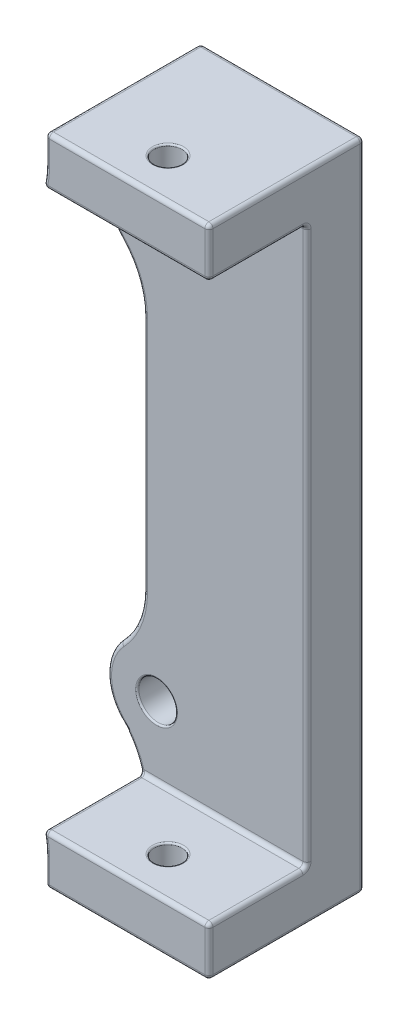
SolidWorks part; units mm, degrees
ref_plane "Front Plane" through (0, 0, 0) normal (0, 0, 1) x (1, 0, 0)
ref_plane "Top Plane" through (0, 0, 0) normal (0, 1, 0) x (1, 0, 0)
ref_plane "Right Plane" through (0, 0, 0) normal (1, 0, 0) x (0, 0, -1)
sketch "Sketch1" plane through (0, 0, 0) normal (0, 0, 1) x (1, 0, 0)
  line L2 (133.4865, -40) -> (139.5, -40) construction
  line L5 (133.4865, 40) -> (139.5, 40) construction
  line L7 (140, -40.5) -> (140, -46.5135) construction
  line L8 (120, 36.5224) -> (120, 40)
  line L9 (140, -40) -> (120, -40)
  line L10 (140, -40) -> (140, 40)
  line L11 (140, 40) -> (120, 40)
  line L12 (120, -40) -> (120, -36.5224)
  line L13 (120, -14.4776) -> (120, 14.4776)
  circle A1 centre (121.5977, 25.5) radius 2.35
  circle A3 centre (121.5977, -25.5) radius 2.35
  arc A4 (117.2486, -21.3666) -> (117.2486, -29.6334) centre (121.5977, -25.5) ccw
  arc A5 (117.2486, 29.6334) -> (117.2486, 21.3666) centre (121.5977, 25.5) ccw
  arc A6 (120, -36.5224) -> (117.2486, -29.6334) centre (110, -36.5224) ccw
  arc A7 (120, -14.4776) -> (117.2486, -21.3666) centre (110, -14.4776) cw
  arc A8 (117.2486, 29.6334) -> (120, 36.5224) centre (110, 36.5224) ccw
  arc A9 (117.2486, 21.3666) -> (120, 14.4776) centre (110, 14.4776) cw
  point P24 (120, 31.2834)
  dimension "D2" = 4.7
  dimension "D3" = 4.7
  dimension "D1" = 10
extrude "Boss-Extrude1" add sketch "Sketch1" along normal blind 7
sketch "Sketch2" plane through (0, 0, 7) normal (0, 0, 1) x (1, 0, 0)
  line L0 (119.6767, 34) -> (140, 34)
  line L1 (140, -34) -> (119.6767, -34)
  line L2 (140, 34) -> (140, 40)
  line L6 (140, -40) -> (140, 40)
  line L7 (140, 40) -> (120, 40)
  line L8 (120, 40) -> (120, 36.5224)
  line L9 (120, 14.4776) -> (120, -14.4776)
  line L10 (120, -36.5224) -> (120, -40)
  line L11 (120, -40) -> (140, -40)
  line L12 (140, -40) -> (140, -34)
  line L13 (140, 40) -> (120, 40)
  line L14 (120, 40) -> (120, 36.5224)
  line L16 (120, -36.5224) -> (120, -40)
  line L17 (120, -40) -> (140, -40)
  arc A6 (117.2486, 29.6334) -> (120, 36.5224) centre (110, 36.5224) ccw
  arc A7 (117.2486, 29.6334) -> (117.2486, 21.3666) centre (121.5977, 25.5) ccw
  arc A8 (120, 14.4776) -> (117.2486, 21.3666) centre (110, 14.4776) ccw
  arc A9 (117.2486, -21.3666) -> (120, -14.4776) centre (110, -14.4776) ccw
  arc A10 (117.2486, -21.3666) -> (117.2486, -29.6334) centre (121.5977, -25.5) ccw
  arc A11 (120, -36.5224) -> (117.2486, -29.6334) centre (110, -36.5224) ccw
  arc A12 (119.6767, 34) -> (120, 36.5224) centre (110, 36.5224) ccw
  arc A17 (120, -36.5224) -> (119.6767, -34) centre (110, -36.5224) ccw
  dimension "D2" = 6
  dimension "D3" = 6
  dimension "D1" = 0
extrude "Boss-Extrude2" add sketch "Sketch2" along normal blind 12
sketch "Sketch3" plane through (0, 34, 0) normal (0, -1, 0) x (1, 0, 0)
  line L1 (119.6767, 19) -> (140, 19) construction
  line L5 (130, 36.5645) -> (130, 31.7472) construction
  circle A0 centre (130, 14) radius 1.7
  dimension "D1" = 3.4
  dimension "D2" = 5
extrude "Cut-Extrude1" cut sketch "Sketch3" against normal through all and the other way through all
fillet "Fillet1" radius 0.5 40 edges at (118.7397, 31.6626, 7) (115.5977, 25.5, 7) (119.2867, 18.1867, 7) (118.7397, -31.6626, 7) (115.5977, -25.5, 7) (119.2867, -18.1867, 7) (120, 38.2612, 0) (119.2867, 32.8133, 0) (115.5977, 25.5, 0) (119.2867, 18.1867, 0) (120, -38.2612, 0) (119.2867, -32.8133, 0) (115.5977, -25.5, 0) (119.2867, -18.1867, 0) (120, 0, 7) (120, 0, 0) (140, -40, 9.5) (140, -34, 13) (140, 0, 7) (140, 34, 13) (140, 40, 9.5) (140, 0, 0) (120, -38.2612, 19) (119.9188, -35.2509, 19) (129.8383, -34, 19) (140, -37, 19) (130, -40, 19) (140, 37, 19) (129.8383, 34, 19) (119.9188, 35.2509, 19) (120, 38.2612, 19) (130, 40, 19) (120, -40, 9.5) (120, 40, 9.5) (119.6767, 34, 13) (119.6767, -34, 13) (130, -40, 0) (130, 40, 0) (129.8383, 34, 7) (129.8383, -34, 7)
fillet "Fillet2" radius 0.2 8 edges at (131.7, -34, 14) (130, -40, 12.3) (130, 34, 15.7) (130, 40, 12.3) (123.9477, -25.5, 0) (123.9477, -25.5, 7) (123.9477, 25.5, 0) (123.9477, 25.5, 7)
